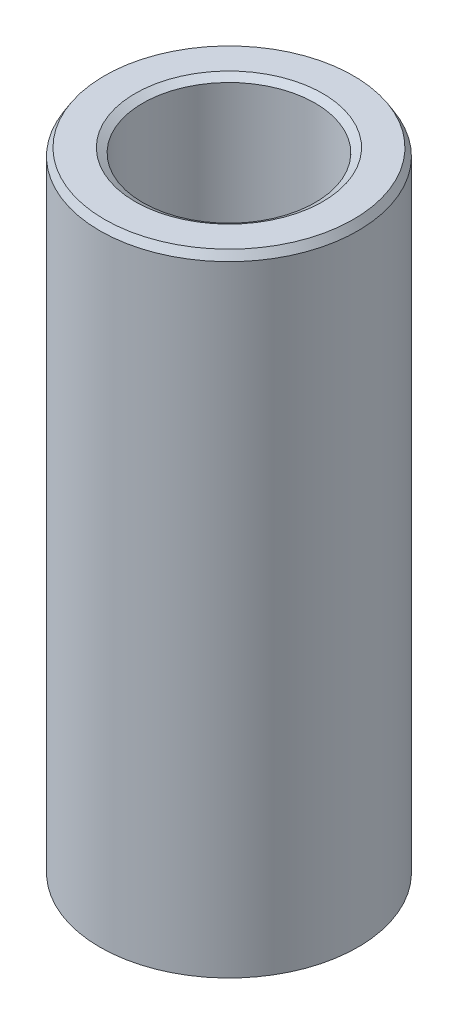
SolidWorks part; units mm, degrees
ref_plane "Front Plane" through (0, 0, 0) normal (0, 0, 1) x (1, 0, 0)
ref_plane "Top Plane" through (0, 0, 0) normal (0, 1, 0) x (1, 0, 0)
ref_plane "Right Plane" through (0, 0, 0) normal (1, 0, 0) x (0, 0, -1)
sketch "Sketch1" plane through (0, 0, 0) normal (0, 1, 0) x (1, 0, 0)
  circle A0 centre (0, 0) radius 60
  dimension "SLEEVE_OD" = 120
extrude "Boss-Extrude1" add sketch "Sketch1" along normal blind 294.109
sketch "Sketch2" plane through (0, 0, 0) normal (0, 1, 0) x (1, 0, 0)
  circle A0 centre (0, 0) radius 40.0763
  dimension "BORE_D" = 80.1525
extrude "Cut-Extrude1" cut sketch "Sketch2" along normal through all
chamfer "Chamfer1" distance 3.5262 angle 31.128 4 edges at (0, 294.109, 40.0763) (0, 0, 40.0763) (0, 0, 60) (0, 294.109, 60) first distance on face at (0, 294.109, 40.0763) first distance on face at (0, 0, 40.0763) first distance on face at (0, 294.109, 60)
